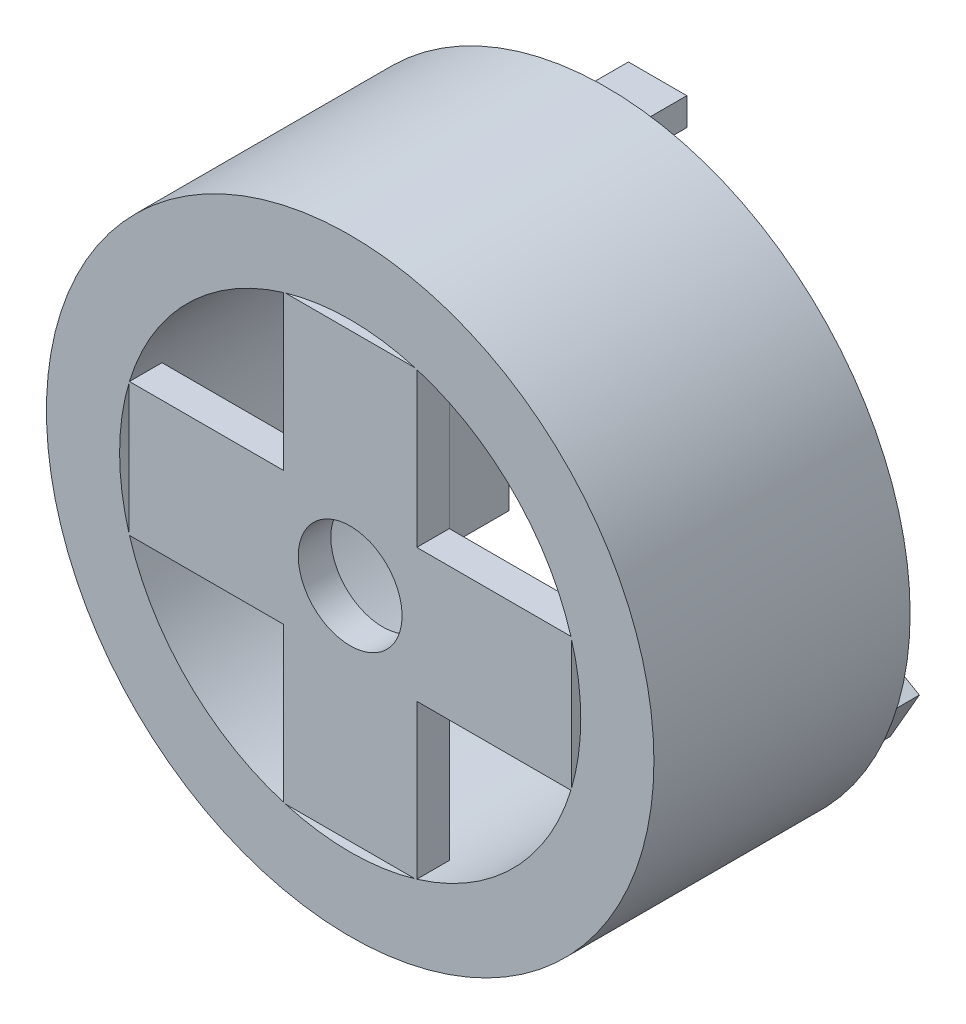
SolidWorks part; units mm, degrees
ref_plane "Front Plane" through (0, 0, 0) normal (0, 0, 1) x (1, 0, 0)
ref_plane "Top Plane" through (0, 0, 0) normal (0, 1, 0) x (1, 0, 0)
ref_plane "Right Plane" through (0, 0, 0) normal (1, 0, 0) x (0, 0, -1)
sketch "Sketch1" plane through (0, 0, 0) normal (0, 0, 1) x (1, 0, 0)
  line L0 (23.5, 0) -> (22.5, 0)
  line L1 (0, 25.15) -> (0, 22.5)
  line L3 (0, -22.5) -> (0, -29.64)
  line L4 (22.5, 0) -> (-22.5, 0)
  line L8 (28.3, 4.9) -> (23.5, 4.9)
  line L9 (28.3, 4.9) -> (28.3, -4.9)
  line L10 (28.3, -4.9) -> (23.5, -4.9)
  line L11 (23.5, 4.9) -> (23.5, -4.9)
  line L24 (-2.85, 27.85) -> (-2.85, 25.15)
  line L25 (-2.85, 27.85) -> (2.85, 27.85)
  line L26 (2.85, 27.85) -> (2.85, 25.15)
  line L27 (-2.85, 25.15) -> (2.85, 25.15)
  circle A0 centre (0, 0) radius 22.5
  circle A1 centre (0, 0) radius 29.64
  point P0 (0, 25.15)
  point P1 (23.5, 0)
  dimension "D3" = 5.7
  dimension "D1" = 1
  dimension "D2" = 2.65
  dimension "D4" = 2.7
extrude "Boss-Extrude1" add sketch "Sketch1" along normal blind 25 contours A1 L11 L8 L9 L10 L27 L24 L25 L26 A0 | L24 L27 L26 L25 | L8 L11 L10 L9 | L3 A1 L9 L10 L11 L0 A0 region at (-20.3658, 20.3658, 0) region at (0, 26.5, 0) region at (25.9, 0, 0)
extrude "Boss-Extrude2" add sketch "Sketch1<4>" against normal blind 5 contours L25 L26 L27 L24
sketch "Sketch1<4>" plane through (0, 0, 0) normal (0, 0, 1) x (1, 0, 0) same geometry as "Sketch1"
sketch "Sketch3" plane through (0, 0, 0) normal (0, 1, 0) x (1, 0, 0)
  line L0 (0, -26.5014) -> (0, 0)
pattern_circular "CirPattern2" count 3 over 360 about axis through (0, 0, 26.5014) along (0, 0, -1) of "Boss-Extrude2" reverse direction yes
sketch "Sketch4" plane through (0, 0, 25) normal (0, 0, 1) x (1, 0, 0)
  line L1 (6.5008, -21.5911) -> (-6.5008, -21.5911)
  line L2 (6.5008, -21.5911) -> (6.5008, 21.5911)
  line L3 (6.5008, 21.5911) -> (-6.5008, 21.5911)
  line L4 (-6.5008, -21.5911) -> (-6.5008, 21.5911)
  line L5 (6.5008, -21.5911) -> (-6.5008, 21.5911) construction
  line L6 (6.5008, 21.5911) -> (-6.5008, -21.5911) construction
  line L7 (-21.5911, 6.5008) -> (21.5911, 6.5008)
  line L8 (-21.5911, 6.5008) -> (-21.5911, -6.5008)
  line L9 (-21.5911, -6.5008) -> (21.5911, -6.5008)
  line L10 (21.5911, 6.5008) -> (21.5911, -6.5008)
  line L11 (-21.5911, 6.5008) -> (21.5911, -6.5008) construction
  line L12 (-21.5911, -6.5008) -> (21.5911, 6.5008) construction
  point P0 (0, 0)
  point P5 (0, 0)
  circle M5 centre (0, 0) radius 22.5
extrude "Boss-Extrude3" add sketch "Sketch4" against normal blind 3.175 contours L2 L9 L7 M5 | L9 L4 L2 M5 | L9 L10 L7 L8 | L2 L3 L4 L1 region at (0, -14.0456, 25) region at (14.0456, 0, 25)
sketch "Sketch7" plane through (0, 0, 25) normal (0, 0, 1) x (1, 0, 0)
  circle A0 centre (0, 0) radius 5.0625
extrude "Cut-Extrude2" cut sketch "Sketch7" against normal up to next and the other way through all
sketch "Sketch8" plane through (0, 0, 25) normal (0, 0, 1) x (1, 0, 0)
  line L5 (6.5, 18.1018) -> (-6.5, 18.1018)
  line L6 (6.5, 18.1018) -> (6.5, 5.1018)
  line L11 (6.5, 5.1018) -> (-6.5, 5.1018)
  line L12 (-6.5, 18.1018) -> (-6.5, 5.1018)
  line L13 (6.5, 18.1018) -> (-6.5, 5.1018) construction
  line L14 (6.5, 5.1018) -> (-6.5, 18.1018) construction
  point P0 (0, 11.6018)
  point P5 (0, 0)
  point P6 (0, 0)
  point P7 (0, 10.2992)
  point P8 (0, 12.0548)
  point P9 (-4.9, 15.4742)
  point P10 (0, 13.4162)
  point P11 (4.9, 14.8625)
  point P12 (6.5, 6.7776)
  point P13 (0, 10.2992)
  dimension "D1" = 13
  dimension "D2" = 13
extrude "Boss-Extrude4" add sketch "Sketch8" against normal blind 9 contours L5 L12 L11 L6 region at (0, 11.6018, 25)
extrude "Cut-Extrude1" cut sketch "Sketch1<3>" along normal blind 23 contours L8 L11 L10 L9 region at (25.9, 0, 0)
sketch "Sketch1<3>" plane through (0, 0, 0) normal (0, 0, 1) x (1, 0, 0) same geometry as "Sketch1"
pattern_circular "CirPattern1" count 6 over 360 about axis through (0, 0, 26.5014) along (0, 0, -1) of "Cut-Extrude1" reverse direction yes
sketch "Sketch9" plane through (0, 0, 25) normal (0, 0, 1) x (1, 0, 0)
  line L0 (0, 5.0625) -> (0, 6.0625)
  line L1 (4.9, 15.8625) -> (-4.9, 15.8625)
  line L2 (4.9, 15.8625) -> (4.9, 6.0625)
  line L3 (4.9, 6.0625) -> (-4.9, 6.0625)
  line L4 (-4.9, 15.8625) -> (-4.9, 6.0625)
  line L5 (4.9, 15.8625) -> (-4.9, 6.0625) construction
  line L6 (4.9, 6.0625) -> (-4.9, 15.8625) construction
  circle A0 centre (0, 0) radius 5.0625 construction
  point P0 (0, 10.9625)
  dimension "D1" = 9.8
  dimension "D2" = 9.8
